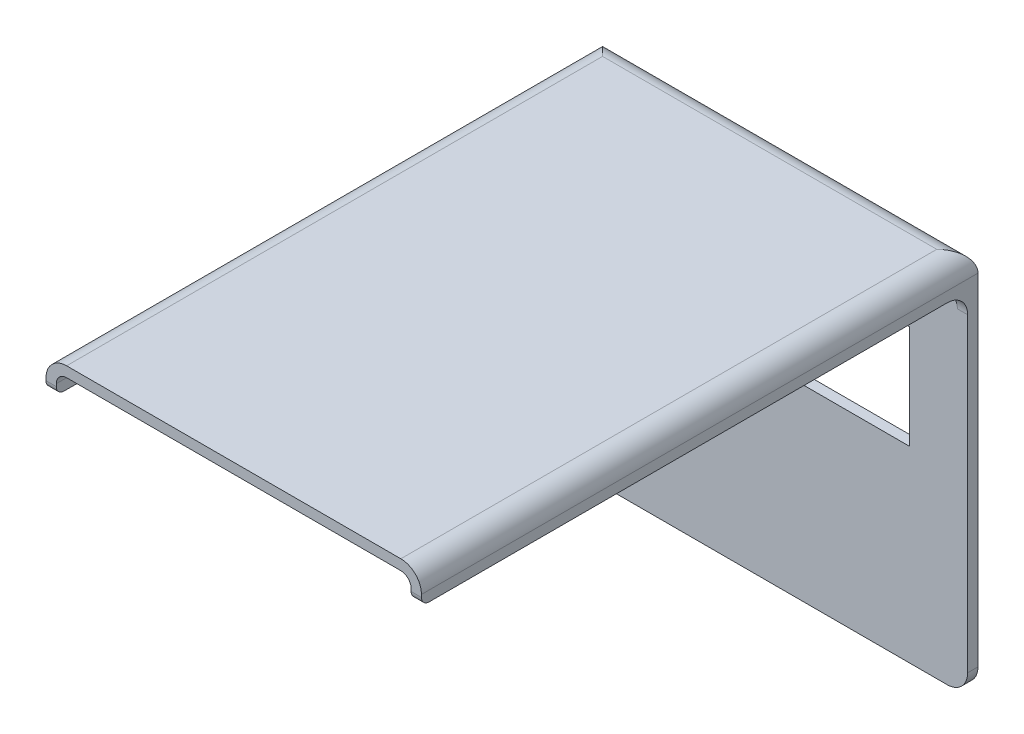
SolidWorks part; units mm, degrees
ref_plane "Front Plane" through (0, 0, 0) normal (0, 0, 1) x (1, 0, 0)
ref_plane "Top Plane" through (0, 0, 0) normal (0, 1, 0) x (1, 0, 0)
ref_plane "Right Plane" through (0, 0, 0) normal (1, 0, 0) x (0, 0, -1)
sketch "Sketch1" plane through (0, 0, 0) normal (0, 1, 0) x (1, 0, 0)
  line L1 (-34.425, -53.5) -> (34.425, -53.5)
  line L2 (-34.425, -53.5) -> (-34.425, 53.5)
  line L3 (-34.425, 53.5) -> (34.425, 53.5)
  line L4 (34.425, -53.5) -> (34.425, 53.5)
  line L5 (-34.425, -53.5) -> (34.425, 53.5) construction
  line L6 (-34.425, 53.5) -> (34.425, -53.5) construction
  point P0 (0, 0)
  dimension "D1" = 68.85
  dimension "D2" = 107
extrude "Boss-Extrude1" add sketch "Sketch1" along normal blind 2
sketch "Sketch2" plane through (0, 0, 0) normal (0, -1, 0) x (1, 0, 0)
  line L0 (34.425, 53.5) -> (34.425, -53.5) construction
  line L1 (-34.425, -53.5) -> (34.425, -53.5)
  line L2 (-34.425, -53.5) -> (-34.425, -51.5)
  line L3 (-34.425, -51.5) -> (34.425, -51.5)
  line L4 (34.425, -53.5) -> (34.425, -51.5)
  dimension "D1" = 2
extrude "Boss-Extrude2" add sketch "Sketch2" along normal blind 67
sketch "Sketch4" plane through (0, 0, -53.5) normal (0, 0, -1) x (-1, 0, 0)
  line L1 (-7.05, -15.85) -> (-7.05, -21.15) construction
  line L2 (-24.95, -15.85) -> (-7.05, -15.85) construction
  line L3 (-24.95, -15.85) -> (-24.95, -35.55) construction
  line L4 (-24.95, -35.55) -> (24.95, -35.55) construction
  line L5 (24.95, -15.85) -> (24.95, -35.55) construction
  line L7 (7.05, -15.85) -> (7.05, -21.15) construction
  line L10 (-5.325, -21.15) -> (7.05, -21.15) construction
  line L11 (-5.325, -21.15) -> (-7.05, -21.15) construction
  line L12 (7.05, -15.85) -> (24.95, -15.85) construction
  line L13 (-7.05, -15.85) -> (-7.05, -35.55) construction
  line L14 (7.05, -15.85) -> (7.05, -35.55) construction
  line L15 (-6.85, -15.65) -> (-6.85, -20.95)
  line L16 (-5.325, -20.95) -> (-6.85, -20.95)
  line L17 (-5.325, -20.95) -> (6.85, -20.95)
  line L18 (6.85, -15.65) -> (6.85, -20.95)
  line L19 (6.85, -15.65) -> (25.15, -15.65)
  line L20 (25.15, -15.65) -> (25.15, -35.75)
  line L21 (-25.15, -35.75) -> (25.15, -35.75)
  line L22 (-25.15, -15.65) -> (-25.15, -35.75)
  line L23 (-25.15, -15.65) -> (-6.85, -15.65)
  dimension "D1" = 0.2
extrude "Cut-Extrude2" cut sketch "Sketch4" against normal up to next
sketch "Sketch5" plane through (0, 0, -51.5) normal (0, 0, 1) x (1, 0, 0)
  line L0 (34.425, -67) -> (34.425, 0) construction
  line L1 (-34.425, -67) -> (34.425, -67)
  line L2 (-34.425, -67) -> (-34.425, -65)
  line L3 (-34.425, -65) -> (34.425, -65)
  line L4 (34.425, -67) -> (34.425, -65)
  line L5 (-34.425, -67) -> (-34.425, 0) construction
  dimension "D1" = 2
extrude "Boss-Extrude3" add sketch "Sketch5" along normal blind 51
sketch "Sketch6" plane through (0, -67, 0) normal (0, -1, 0) x (1, 0, 0)
  line L0 (34.425, -53.5) -> (34.425, -0.5) construction
  line L1 (-34.425, -0.5) -> (34.425, -0.5)
  line L2 (-34.425, -0.5) -> (-34.425, -2.5)
  line L3 (-34.425, -2.5) -> (34.425, -2.5)
  line L4 (34.425, -0.5) -> (34.425, -2.5)
  line L5 (-34.425, -0.5) -> (-34.425, -53.5) construction
  dimension "D1" = 2
extrude "Boss-Extrude4" add sketch "Sketch6" along normal blind 20.36
sketch "Sketch8" plane through (0, 2, 0) normal (0, 1, 0) x (1, 0, 0)
  line L6 (34.425, 53.5) -> (-34.425, 53.5) construction
  line L7 (-36.425, 50.5) -> (-34.425, 50.5)
  line L8 (-34.425, 53.5) -> (-34.425, -53.5) construction
  line L9 (36.425, -55.5) -> (36.425, 53.5)
  line L10 (-36.425, -55.5) -> (36.425, -55.5)
  line L11 (-36.425, 53.5) -> (-36.425, -55.5)
  line L12 (36.425, -55.5) -> (36.425, 50.5)
  line L13 (-36.425, -55.5) -> (36.425, -55.5)
  line L14 (-36.425, 50.5) -> (-36.425, -55.5)
  line L15 (34.425, 50.5) -> (36.425, 50.5)
  line L16 (34.425, -53.5) -> (34.425, 53.5) construction
  line L21 (34.425, -53.5) -> (34.425, 53.5)
  line L22 (34.425, 53.5) -> (-34.425, 53.5)
  line L23 (-34.425, 53.5) -> (-34.425, -53.5)
  line L24 (-34.425, -53.5) -> (34.425, -53.5)
  line L25 (34.425, -53.5) -> (34.425, 50.5)
  line L27 (-34.425, 50.5) -> (-34.425, -53.5)
  line L28 (-34.425, -53.5) -> (34.425, -53.5)
  dimension "D2" = 3
  dimension "D3" = 3
  dimension "D1" = 2
  dimension "D4" = 0
extrude "Boss-Extrude5" add sketch "Sketch8" against normal blind 1.5
sketch "Sketch13" plane through (0, 0, -50.5) normal (0, 0, -1) x (-1, 0, 0)
  line L4 (36.425, 2) -> (34.425, 2)
  line L5 (34.425, 2) -> (34.425, 0.5)
  line L6 (34.425, 0.5) -> (36.425, 0.5)
  line L7 (36.425, 0.5) -> (36.425, 2)
  line L8 (36.425, 2) -> (34.425, 2)
  line L9 (34.425, 2) -> (34.425, 0.5)
  line L10 (34.425, 0.5) -> (36.425, 0.5)
  line L11 (36.425, 0.5) -> (36.425, 2)
  line L12 (-34.425, 2) -> (-36.425, 2)
  line L13 (-36.425, 2) -> (-36.425, 0.5)
  line L14 (-36.425, 0.5) -> (-34.425, 0.5)
  line L15 (-34.425, 0.5) -> (-34.425, 2)
  line L16 (-34.425, 2) -> (-36.425, 2)
  line L17 (-36.425, 2) -> (-36.425, 0.5)
  line L18 (-36.425, 0.5) -> (-34.425, 0.5)
  line L19 (-34.425, 0.5) -> (-34.425, 2)
  dimension "D1" = 0
  dimension "D2" = 0
extrude "Boss-Extrude8" add sketch "Sketch13" along normal up to surface (3 mm away) up to face at (0, -22, -53.5)
sketch "Sketch9" plane through (0, -67, 0) normal (0, -1, 0) x (1, 0, 0)
  line L2 (-34.425, -2.5) -> (34.425, -2.5) construction
  line L3 (0, 0) -> (0, -58.5995) construction
  circle A0 centre (-25, -23.48) radius 1.75
  circle A1 centre (25, -23.48) radius 1.75
  dimension "D1" = 3.5
  dimension "D2" = 50
  dimension "D5" = 3.5
  dimension "D4" = 20.98
extrude "Cut-Extrude4" cut sketch "Sketch9" against normal up to next
fillet "Fillet1" radius 1.5 1 edges
fillet "Fillet2" radius 3 1 edges at (0, -65, -0.5)
fillet "Fillet3" radius 1.5 1 edges at (0, -65, -51.5)
fillet "Fillet4" radius 3 1 edges at (0, -67, -53.5)
sketch "Sketch10" plane through (0, 0, -0.5) normal (0, 0, 1) x (1, 0, 0)
  line L0 (34.425, -87.36) -> (-34.425, -87.36) construction
  line L1 (-34.425, -68) -> (-34.425, -87.36) construction
  line L2 (34.425, -87.36) -> (34.425, -68) construction
  circle A0 centre (-24.425, -79.36) radius 1.75
  circle A1 centre (24.425, -79.36) radius 1.75
  dimension "D1" = 8
  dimension "D2" = 3.5
  dimension "D4" = 3.5
  dimension "D5" = 10
  dimension "D3" = 10
  dimension "D6" = 8
extrude "Cut-Extrude5" cut sketch "Sketch10" against normal up to next
chamfer "Chamfer1" distance 2 angle 45 2 edges at (-34.425, -87.36, -1.5) (34.425, -87.36, -1.5)
sketch "Sketch11" plane through (0, 0.5, 0) normal (0, -1, 0) x (1, 0, 0)
  line L0 (-36.425, 55.5) -> (36.425, 55.5) construction
  line L1 (36.425, -53.5) -> (34.425, -53.5)
  line L2 (36.425, -53.5) -> (36.425, 55.5)
  line L3 (36.425, 55.5) -> (34.425, 55.5)
  line L4 (34.425, -53.5) -> (34.425, 55.5)
  line L5 (34.425, 53.5) -> (34.425, -51.5) construction
  line L6 (-34.425, -50.5) -> (-34.425, -53.5) construction
  line L7 (-36.425, 55.5) -> (-34.425, 55.5)
  line L8 (-36.425, 55.5) -> (-36.425, -53.5)
  line L9 (-36.425, -53.5) -> (-34.425, -53.5)
  line L10 (-34.425, 55.5) -> (-34.425, -53.5)
extrude "Boss-Extrude6" add sketch "Sketch11" along normal blind 4.5
sketch "Sketch14" plane through (0, 0, 53.5) normal (0, 0, 1) x (1, 0, 0)
  line L4 (34.425, 0.5) -> (-34.425, 0.5)
  line L5 (-34.425, 0.5) -> (-34.425, 0)
  line L6 (-34.425, 0) -> (34.425, 0)
  line L7 (-34.425, 0.5) -> (-34.425, 0)
  line L8 (34.425, 0.5) -> (-34.425, 0.5)
  line L9 (34.425, 0) -> (34.425, 0.5)
  line L10 (-34.425, 0) -> (34.425, 0)
  line L11 (34.425, 0) -> (34.425, 0.5)
  dimension "D1" = 0
extrude "Boss-Extrude9" add sketch "Sketch14" along normal up to surface (2 mm away) up to face at (0, -1.375, 55.5)
fillet "Fillet5" radius 2 3 edges
fillet "Fillet6" radius 4 1 edges at (0, 2, -53.5)
fillet "Fillet8" radius 4 2 edges at (-36.425, 2, 3) (36.425, 2, 3)
sketch "Sketch15" plane through (0, 0, 55.5) normal (0, 0, 1) x (1, 0, 0)
  line L6 (-36.425, -2) -> (-36.425, -4)
  line L7 (-36.425, -2) -> (-36.425, -4)
  line L8 (32.425, 2) -> (-32.425, 2)
  line L9 (-36.425, -4) -> (-34.425, -4)
  line L10 (-36.425, -4) -> (-34.425, -4)
  line L11 (-34.425, -4) -> (-34.425, -2)
  line L12 (-32.425, 0) -> (32.425, 0)
  line L13 (-34.425, -4) -> (-34.425, -2)
  line L14 (34.425, -2) -> (34.425, -4)
  line L15 (34.425, -2) -> (34.425, -4)
  line L16 (32.425, 2) -> (-32.425, 2)
  line L19 (34.425, -4) -> (36.425, -4)
  line L20 (-32.425, 0) -> (32.425, 0)
  line L21 (34.425, -4) -> (36.425, -4)
  line L22 (36.425, -4) -> (36.425, -2)
  line L23 (36.425, -4) -> (36.425, -2)
  arc A4 (-32.425, 2) -> (-36.425, -2) centre (-32.425, -2) ccw
  arc A5 (-32.425, 0) -> (-34.425, -2) centre (-32.425, -2) ccw
  arc A6 (-32.425, 0) -> (-34.425, -2) centre (-32.425, -2) ccw
  arc A7 (36.425, -2) -> (32.425, 2) centre (32.425, -2) ccw
  arc A8 (-32.425, 2) -> (-36.425, -2) centre (-32.425, -2) ccw
  arc A9 (34.425, -2) -> (32.425, 0) centre (32.425, -2) ccw
  arc A10 (34.425, -2) -> (32.425, 0) centre (32.425, -2) ccw
  arc A11 (36.425, -2) -> (32.425, 2) centre (32.425, -2) ccw
  dimension "D1" = 0
extrude "Cut-Extrude6" cut sketch "Sketch15" against normal blind 1
sketch "Sketch16" plane through (34.425, 0, 0) normal (1, 0, 0) x (0, 0, -1)
  line L0 (2.5, -87.36) -> (0.5, -87.36) construction
  line L1 (2.5, -87.36) -> (0.5, -87.36)
  line L2 (51.5, -63.5) -> (53.5, -63.5)
  line L8 (53.5, -64) -> (53.5, -4)
  line L9 (53.5, -4) -> (51.5, -4)
  line L10 (51.5, -4) -> (51.5, -63.5)
  line L11 (50, -65) -> (3.5, -65)
  line L12 (0.5, -68) -> (0.5, -85.36)
  line L13 (0.5, -85.36) -> (2.5, -85.36)
  line L14 (2.5, -85.36) -> (2.5, -68.5)
  line L15 (4, -67) -> (50.5, -67)
  line L16 (53.5, -64) -> (53.5, -63.5)
  line L19 (50, -65) -> (3.5, -65)
  line L20 (0.5, -68) -> (0.5, -87.36)
  line L22 (2.5, -87.36) -> (2.5, -68.5)
  line L23 (4, -67) -> (50.5, -67)
  arc A4 (50, -65) -> (51.5, -63.5) centre (50, -63.5) ccw
  arc A5 (3.5, -65) -> (0.5, -68) centre (3.5, -68) ccw
  arc A6 (4, -67) -> (2.5, -68.5) centre (4, -68.5) ccw
  arc A7 (50.5, -67) -> (53.5, -64) centre (50.5, -64) ccw
  arc A8 (50, -65) -> (51.5, -63.5) centre (50, -63.5) ccw
  arc A9 (3.5, -65) -> (0.5, -68) centre (3.5, -68) ccw
  arc A10 (4, -67) -> (2.5, -68.5) centre (4, -68.5) ccw
  arc A11 (50.5, -67) -> (53.5, -64) centre (50.5, -64) ccw
  dimension "D1" = 0
extrude "Cut-Extrude7" cut sketch "Sketch16" against normal through all
sketch "Sketch17" plane through (0, -63.5, 0) normal (0, -1, 0) x (1, 0, 0)
  line L4 (-34.425, -53.5) -> (34.425, -53.5)
  line L5 (34.425, -53.5) -> (34.425, -51.5)
  line L6 (34.425, -51.5) -> (-34.425, -51.5)
  line L7 (-34.425, -51.5) -> (-34.425, -53.5)
  line L8 (-34.425, -53.5) -> (34.425, -53.5)
  line L9 (34.425, -53.5) -> (34.425, -51.5)
  line L10 (34.425, -51.5) -> (-34.425, -51.5)
  line L11 (-34.425, -51.5) -> (-34.425, -53.5)
  dimension "D1" = 0
extrude "Boss-Extrude10" add sketch "Sketch17" along normal blind 8.66
sketch "Sketch18" plane through (34.425, 0, 0) normal (1, 0, 0) x (0, 0, -1)
  line L4 (51.5, -4) -> (51.5, -72.16)
  line L5 (51.5, -72.16) -> (53.5, -72.16)
  line L6 (53.5, -72.16) -> (53.5, -4)
  line L7 (53.5, -4) -> (51.5, -4)
  line L8 (51.5, -4) -> (51.5, -72.16)
  line L9 (51.5, -72.16) -> (53.5, -72.16)
  line L10 (53.5, -72.16) -> (53.5, -4)
  line L11 (53.5, -4) -> (51.5, -4)
  dimension "D1" = 0
extrude "Boss-Extrude11" add sketch "Sketch18" along normal up to surface (2 mm away) up to face at (36.425, -3, 0.5)
sketch "Sketch19" plane through (-34.425, 0, 0) normal (-1, 0, 0) x (0, 0, 1)
  line L4 (-53.5, -4) -> (-53.5, -72.16)
  line L5 (-53.5, -72.16) -> (-51.5, -72.16)
  line L6 (-51.5, -72.16) -> (-51.5, -4)
  line L7 (-51.5, -4) -> (-53.5, -4)
  line L8 (-53.5, -4) -> (-53.5, -72.16)
  line L9 (-53.5, -72.16) -> (-51.5, -72.16)
  line L10 (-51.5, -72.16) -> (-51.5, -4)
  line L11 (-51.5, -4) -> (-53.5, -4)
  dimension "D1" = 0
extrude "Boss-Extrude12" add sketch "Sketch19" along normal up to surface (2 mm away) up to face at (-36.425, -3, 0.5)
fillet "Fillet9" radius 4 2 edges at (-36.425, -72.16, -52.5) (36.425, -72.16, -52.5)
fillet "Fillet10" radius 4 2 edges at (-35.425, -4, -51.5) (35.425, -4, -51.5)
fillet "Fillet11" radius 1.5 2 edges at (-35.425, -4, 54.5) (35.425, -4, 54.5)
